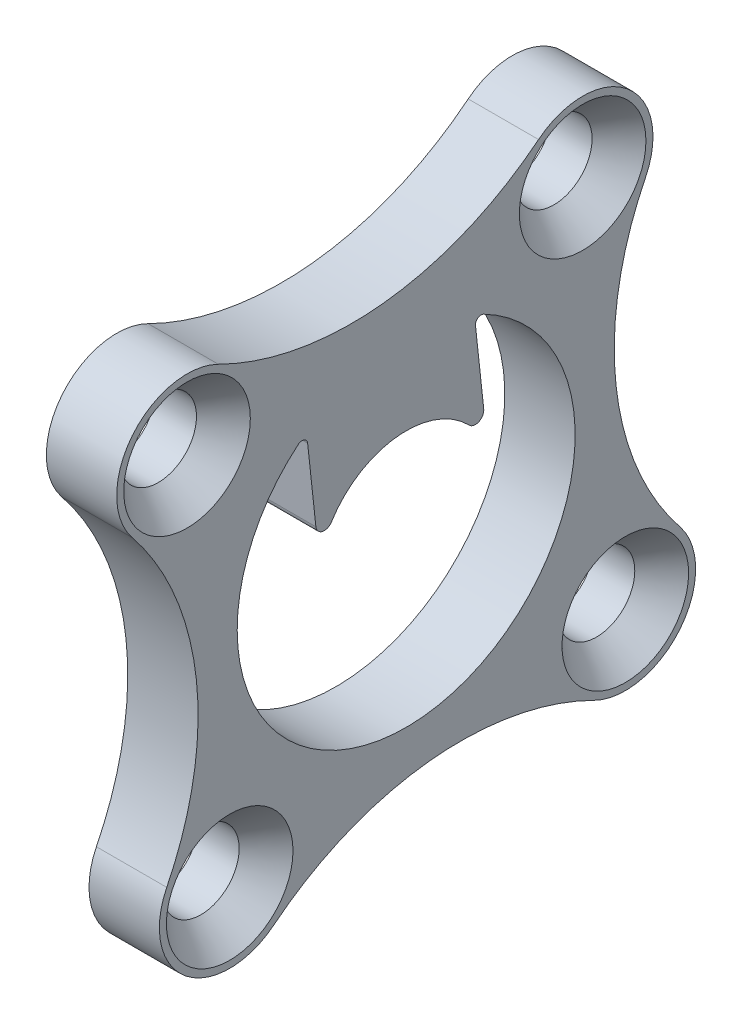
SolidWorks part; units mm, degrees
material "6061-T6 (SS)"
ref_plane "Front Plane" through (0, 0, 0) normal (0, 0, 1) x (1, 0, 0)
ref_plane "Top Plane" through (0, 0, 0) normal (0, 1, 0) x (1, 0, 0)
ref_plane "Right Plane" through (0, 0, 0) normal (1, 0, 0) x (0, 0, -1)
sketch "Sketch1" plane through (-48.665, 0, 0) normal (-1, 0, 0) x (0, 0, 1)
  line L0 (4.4478, 5.7077) -> (4.0751, 2.2522)
  line L1 (4.6292, 7.3892) -> (4.4314, 5.5558) construction
  line L2 (-3.501, 3.0694) -> (-3.1282, 6.525)
  line L3 (-2.9468, 8.2065) -> (-3.4815, 3.2497) construction
  line L5 (4.4314, 5.5558) -> (3.9072, 0.6962) construction
  line L6 (7.9653, -9.8916) -> (-7.9653, 9.8916) construction
  line L7 (-9.8916, -7.9653) -> (9.8916, 7.9653) construction
  arc A0 (4.0751, 2.2522) -> (3.3725, 2.0922) centre (3.6963, 2.293) cw
  arc A1 (3.3725, 2.0922) -> (-2.8487, 2.7633) centre (0, 0) ccw
  arc A2 (-2.8487, 2.7633) -> (-3.501, 3.0694) centre (-3.1222, 3.0286) cw
  circle A3 centre (0, 0) radius 3.9687 construction
  circle A4 centre (0, 0) radius 3.9687 construction
  arc A5 (4.4478, 5.7077) -> (4.8623, 5.8762) centre (4.7004, 5.6805) cw
  arc A8 (4.8623, 5.8762) -> (-3.4972, 6.778) centre (0, 0) cw
  arc A9 (-3.4972, 6.778) -> (-3.1282, 6.525) centre (-3.3807, 6.5522) cw
  circle A10 centre (0, 0) radius 15.875
  arc A11 (-3.5162, 6.6247) -> (4.8482, 5.7223) centre (0, 0) ccw construction
  circle A12 centre (9.8916, 7.9653) radius 3.175 construction
  circle A13 centre (9.8916, 7.9653) radius 2.6924 construction
  circle A14 centre (0, 0) radius 9.525 construction
  dimension "D1" = 0.381
  dimension "D2" = 0.254
  dimension "D3" = 25.4
  dimension "D4" = 0.127
  dimension "D6" = 5.3848
  dimension "D7" = 19.05
  dimension "D5" = 45
extrude "Boss-Extrude1" add sketch "Sketch1" against normal blind 3.175
sketch "Sketch2" plane through (-48.665, 0, 0) normal (-1, 0, 0) x (0, 0, 1)
  line L0 (-9.8916, -7.9653) -> (9.8916, 7.9653) construction
  line L1 (4.4478, 5.7077) -> (4.0751, 2.2522) construction
  line L2 (9.4701, -1.0216) -> (15.7834, -1.7027)
  arc A0 (12.3645, 9.9566) -> (15.7834, -1.7027) centre (0, 0) cw
  circle A1 centre (0, 0) radius 15.875 construction
  circle A3 centre (0, 0) radius 9.525 construction
  arc A5 (12.3658, 5.9755) -> (12.3645, 9.9566) centre (9.8916, 7.9653) ccw
  circle A6 centre (9.8916, 7.9653) radius 3.175 construction
  arc A7 (12.3658, 5.9755) -> (9.4701, -1.0216) centre (22.8627, -2.4664) ccw
extrude "Cut-Extrude1" cut sketch "Sketch2" against normal through all
mirror "Mirror1" about plane through (-45.49, -1.0216, 9.4701) normal (0, -0.9942, -0.1073) of "Cut-Extrude1"
pattern_circular "CirPattern2" count 4 over 360 about axis through (-48.665, 0, 0) along (-1, 0, 0) of "Cut-Extrude1", "Mirror1"
hole_wizard "CSK for #4 Flat Head Machine Screw1" positions "Sketch3" profile "Sketch4" countersink size "#4" standard "ANSI Inch" end condition up to next
sketch "Sketch3" plane through (-45.49, 0, 0) normal (1, 0, 0) x (0, 0, -1)
  point P0 (7.9653, 9.8916)
  point P3 (7.9653, 9.8916)
  point P6 (7.9653, 9.8916)
  point P9 (7.9653, 9.8916)
  point P13 (-9.8916, 7.9653)
  point P16 (-7.9653, -9.8916)
  point P19 (9.8916, -7.9653)
sketch "Sketch4" plane through (-45.49, 9.8916, -7.9653) normal (0, 1, 0) x (0, 0, -1)
  line L0 (0, 0) -> (0, 3.175)
  line L1 (0, 3.175) -> (1.7272, 3.175)
  line L2 (1.7272, 3.175) -> (1.7272, 1.3003)
  line L3 (1.7272, 1.3003) -> (2.8575, 0)
  line L5 (2.8575, 0) -> (0, 0)
  line L6 (-1.7272, 1.3003) -> (-2.8575, 0) construction
  line L11 (0, -6.35) -> (0, 107.95) construction
  dimension "Thru Hole Dia." = 3.4544
  dimension "Thru Hole Depth" = 3.175
  dimension "Near C'Sink Dia." = 5.715
  dimension "Near C'Sink Angle" = 82
